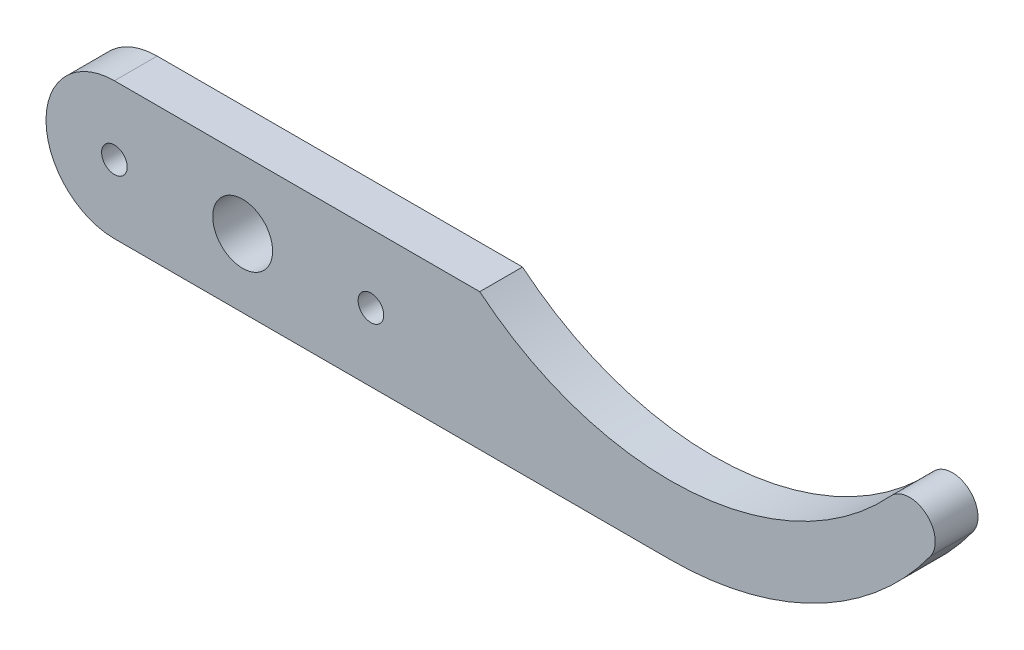
SolidWorks part; units mm, degrees
ref_plane "Plan de face" through (0, 0, 0) normal (0, 0, 1) x (1, 0, 0)
ref_plane "Plan de dessus" through (0, 0, 0) normal (0, 1, 0) x (1, 0, 0)
ref_plane "Plan de droite" through (0, 0, 0) normal (1, 0, 0) x (0, 0, -1)
sketch "Esquisse1" plane through (0, 0, 0) normal (0, 0, 1) x (1, 0, 0)
  line L0 (0, 0) -> (80, 0) construction
  line L1 (20, 0) -> (20, 23.8674) construction
  line L2 (0, 0) -> (0, 35) construction
  line L3 (0, 35) -> (50, 35) construction
  line L4 (0, 8) -> (20, 8)
  line L5 (75.7895, 11.3377) -> (78, 9.3095) construction
  line L6 (20, 8) -> (27.7289, 8)
  line L7 (0, -8) -> (50, -8)
  line L8 (50, 35) -> (50, -8) construction
  line L9 (0, 8) -> (-15, 8)
  line L10 (0, 0) -> (-15, 0) construction
  line L11 (0, -8) -> (-15, -8)
  arc A1 (0, 8) -> (0, -8) centre (0, 0) ccw construction
  circle A2 centre (50, 35) radius 35 construction
  arc A3 (27.7289, 8) -> (75.7895, 11.3377) centre (50, 35) ccw
  arc A4 (75.7895, 11.3377) -> (80.4313, 7.5521) centre (78, 9.3095) cw
  arc A5 (50, -8) -> (80.4313, 7.5521) centre (50, 29.5491) ccw
  circle A6 centre (15, 0) radius 1.5
  arc A7 (-15, 8) -> (-15, -8) centre (-15, 0) ccw
  circle A8 centre (-15, 0) radius 1.5
  circle A9 centre (0, 0) radius 3.5
  dimension "D3" = 3
  dimension "D4" = 35
  dimension "D6" = 70
  dimension "D7" = 3
  dimension "D8" = 8
  dimension "D9" = 28
  dimension "D10" = 15
  dimension "D11" = 8
  dimension "D13" = 3
  dimension "D14" = 7
  dimension "D1" = 20
  dimension "D2" = 80
  dimension "D5" = 50
  dimension "D12" = 15
extrude "Boss.-Extru.1" add sketch "Esquisse1" along normal blind 5
